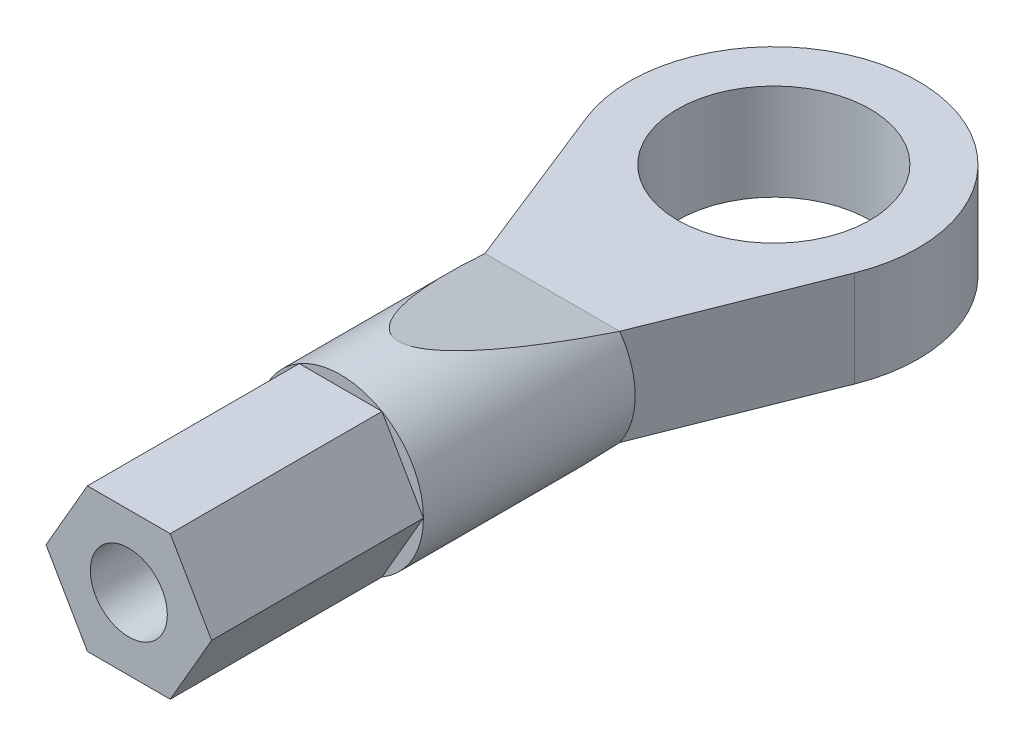
SolidWorks part; units mm, degrees
ref_plane "Front Plane" through (0, 0, 0) normal (0, 0, 1) x (1, 0, 0)
ref_plane "Top Plane" through (0, 0, 0) normal (0, 1, 0) x (1, 0, 0)
ref_plane "Right Plane" through (0, 0, 0) normal (1, 0, 0) x (0, 0, -1)
sketch "Sketch1" plane through (0, 0, 0) normal (0, 1, 0) x (1, 0, 0)
  line L0 (0, -3.75) -> (0, -5.75)
  line L5 (-1.75, -5.75) -> (1.75, -5.75)
  line L6 (1.75, -5.75) -> (3.4848, -1.385)
  line L7 (-1.75, -5.75) -> (-3.4848, -1.385)
  circle A0 centre (0, 0) radius 2.5
  circle A1 centre (0, 0) radius 3.75
  point P4 (0, -3.75)
  point P10 (0, -5.75)
  point P11 (0, -5)
  dimension "D1" = 7.5
  dimension "D2" = 5
  dimension "D3" = 2
  dimension "D4" = 3.5
extrude "Boss-Extrude1" add sketch "Sketch1" along normal blind 2.5 contours A1 A0 | A1 L7 L5 L0 | A1 L0 L5 L6 region at (1.3233, 0, 4.382) region at (-1.3233, 0, 4.382) region at (-2.0462, 0, 3.0152)
sketch "Sketch2" plane through (0, 0, 5.75) normal (0, 0, 1) x (1, 0, 0)
  line L0 (-1.75, 1.25) -> (1.75, 1.25) construction
  line L1 (-1.75, 2.5) -> (-1.75, 0) construction
  line L2 (1.75, 2.5) -> (1.75, 0) construction
  line L3 (0, 0) -> (0, 2.5) construction
  line L4 (-1.75, 2.5) -> (1.75, 2.5) construction
  circle A0 centre (0, 1.25) radius 2.1506
extrude "Boss-Extrude2" add sketch "Sketch2" along normal blind 5.5
sketch "Sketch4" plane through (0, 0, 0) normal (1, 0, 0) x (0, 0, -1)
  line L0 (-11.25, 3.4006) -> (-9.75, 3.4006)
  line L1 (-9.75, 3.4006) -> (-5.75, 2.5)
  line L2 (-5.75, 2.5) -> (-5.75, 0)
  line L3 (-5.75, 0) -> (-9.75, -0.9006)
  line L4 (-11.25, -0.9006) -> (-5.75, -0.9006) construction
  line L5 (-9.75, -0.9006) -> (-11.25, -0.9006)
  line L6 (-9.75, 3.4006) -> (-5.75, 3.4006)
  line L7 (-5.75, 3.4006) -> (-5.75, 2.5)
  line L8 (-5.75, 0) -> (-5.75, -0.9006)
  line L9 (-5.75, -0.9006) -> (-9.75, -0.9006)
  dimension "D1" = 1.5
extrude "Cut-Extrude1" cut sketch "Sketch4" against normal blind 5.5 and the other way blind 5.5 contours L9 L8 L3 | L7 L6 L1 region at (0, 3.1004, 7.0833) region at (0, -0.6004, 7.0833)
sketch "Sketch5" plane through (0, 0, 11.25) normal (0, 0, 1) x (1, 0, 0)
  line L0 (-2.1506, 1.25) -> (2.1506, 1.25) construction
  line L1 (0, -0.9006) -> (0, 3.4006) construction
  line L3 (2.1506, 1.25) -> (1.0753, 3.1125)
  line L4 (1.0753, 3.1125) -> (-1.0753, 3.1125)
  line L5 (-1.0753, 3.1125) -> (-2.1506, 1.25)
  line L6 (-2.1506, 1.25) -> (-1.0753, -0.6125)
  line L7 (-1.0753, -0.6125) -> (1.0753, -0.6125)
  line L8 (1.0753, -0.6125) -> (2.1506, 1.25)
  circle A0 centre (0, 1.25) radius 2.1506 construction
  circle A1 centre (0, 1.25) radius 1.8625 construction
  circle A2 centre (0, 1.25) radius 1
  dimension "D1" = 2
extrude "Boss-Extrude4" add sketch "Sketch5" along normal blind 5.5 contours L3 L4 L5 L6 L7 L8 | A2
